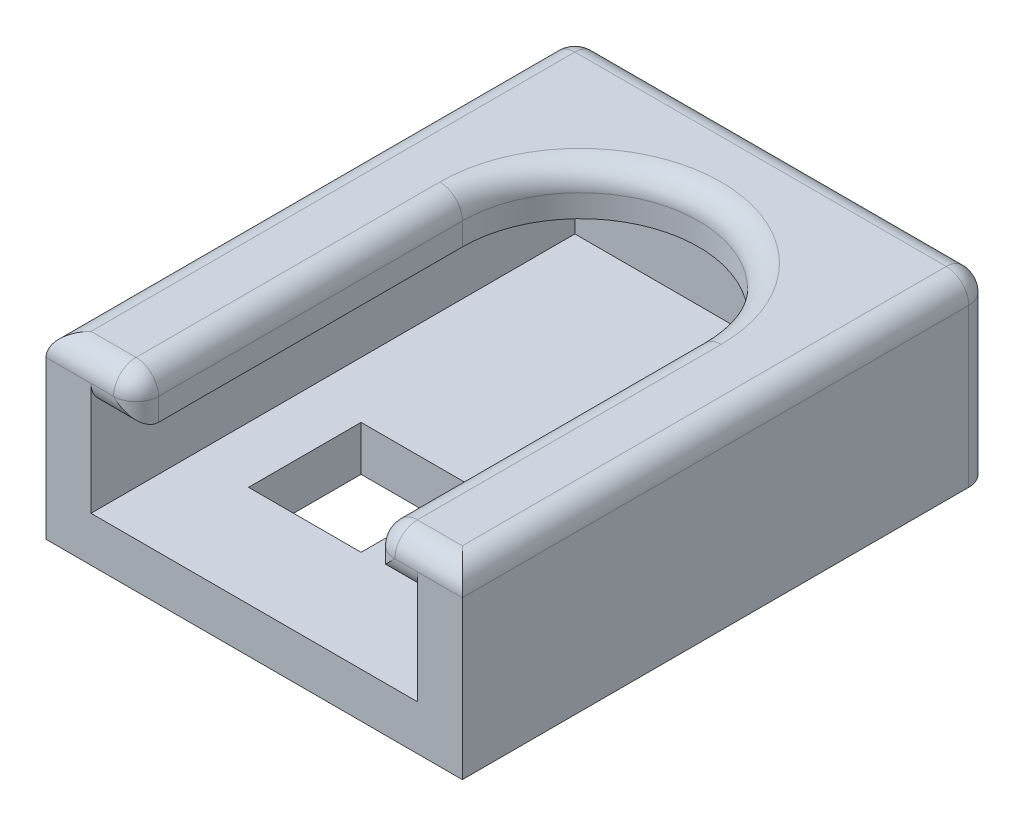
SolidWorks part; units mm, degrees
ref_plane "Front Plane" through (0, 0, 0) normal (0, 0, 1) x (1, 0, 0)
ref_plane "Top Plane" through (0, 0, 0) normal (0, 1, 0) x (1, 0, 0)
ref_plane "Right Plane" through (0, 0, 0) normal (1, 0, 0) x (0, 0, -1)
sketch "Sketch1" plane through (0, 0, 0) normal (0, 1, 0) x (1, 0, 0)
  line L1 (-7.25, 10.75) -> (7.25, 10.75)
  line L2 (-7.25, 10.75) -> (-7.25, -10.75)
  line L3 (-7.25, -10.75) -> (7.25, -10.75)
  line L4 (7.25, 10.75) -> (7.25, -10.75)
  line L5 (-7.25, 10.75) -> (7.25, -10.75) construction
  line L6 (-7.25, -10.75) -> (7.25, 10.75) construction
  point P0 (0, 0)
  dimension "D1" = 21.5
  dimension "D2" = 14.5
extrude "Boss-Extrude1" add sketch "Sketch1" along normal blind 6
shell "Shell1" thickness 2 removed face at (0, 3, 10.75) removed face at (0, 6, 0) outward yes
sketch "Sketch3" plane through (0, 6, 0) normal (0, 1, 0) x (1, 0, 0)
  line L6 (-7.25, 10.75) -> (-7.25, -10.75) construction
  line L7 (-7.25, 3.75) -> (-5.25, 3.75)
  line L8 (-7.25, 3.75) -> (-7.25, -10.75)
  line L9 (-7.25, -10.75) -> (-5.25, -10.75)
  line L10 (-5.25, 3.75) -> (-5.25, -10.75)
  line L11 (-7.25, -10.75) -> (7.25, -10.75) construction
  line L12 (0, 10.75) -> (0, -10.75) construction
  line L13 (7.25, 10.75) -> (-7.25, 10.75) construction
  line L14 (5.25, 3.75) -> (5.25, -10.75)
  line L15 (7.25, -10.75) -> (5.25, -10.75)
  line L16 (7.25, 3.75) -> (7.25, -10.75)
  line L17 (7.25, 3.75) -> (5.25, 3.75)
  line L18 (-5.25, 3.75) -> (5.25, 3.75) construction
  line L19 (-7.25, 3.75) -> (-7.25, 10.75)
  line L20 (-7.25, 10.75) -> (7.25, 10.75)
  line L21 (7.25, 10.75) -> (7.25, 3.75)
  circle A0 centre (0, 3.75) radius 5.25
  line M2 (7.25, 10.75) -> (7.25, -10.75)
  line M8 (-7.25, -10.75) -> (-7.25, 10.75)
  line M9 (-7.25, 10.75) -> (7.25, 10.75)
  dimension "D3" = 10.5
  dimension "D1" = 14.5
  dimension "D2" = 2
extrude "Boss-Extrude3" add sketch "Sketch3" against normal blind 2 contours A0 L17 L7 M2 M9 M8 | L10 L7 L9 M8 | L17 L14 L15 M2 region at (-7.089, 6, -7.25) region at (-6.25, 6, 3.5) region at (6.25, 6, 3.5)
sketch "Sketch4" plane through (0, 0, 0) normal (0, 1, 0) x (1, 0, 0)
  line L1 (-4.75, -1.25) -> (0.25, -1.25)
  line L2 (-4.75, -1.25) -> (-4.75, -6.25)
  line L3 (-4.75, -6.25) -> (0.25, -6.25)
  line L4 (0.25, -1.25) -> (0.25, -6.25)
  line L5 (9.25, 12.75) -> (-9.25, 12.75) construction
  line L6 (-9.25, 12.75) -> (-9.25, -10.75) construction
  dimension "D1" = 5
  dimension "D2" = 5
  dimension "D3" = 4.5
  dimension "D4" = 14
extrude "Cut-Extrude1" cut sketch "Sketch4" against normal up to surface (2 mm away) up to face at (0, -2, -1)
fillet "Fillet1" radius 1 14 edges at (5.25, 6, 3.5) (0, 6, -9) (-6.25, 4, 10.75) (6.25, 4, 10.75) (5.25, 5, 10.75) (-5.25, 5, 10.75) (-5.25, 6, 3.5) (-7.25, 6, 10.75) (7.25, 6, 10.75) (9.25, 6, -1) (0, 6, -12.75) (-9.25, 6, -1) (9.25, 2, -12.75) (-9.25, 2, -12.75)
